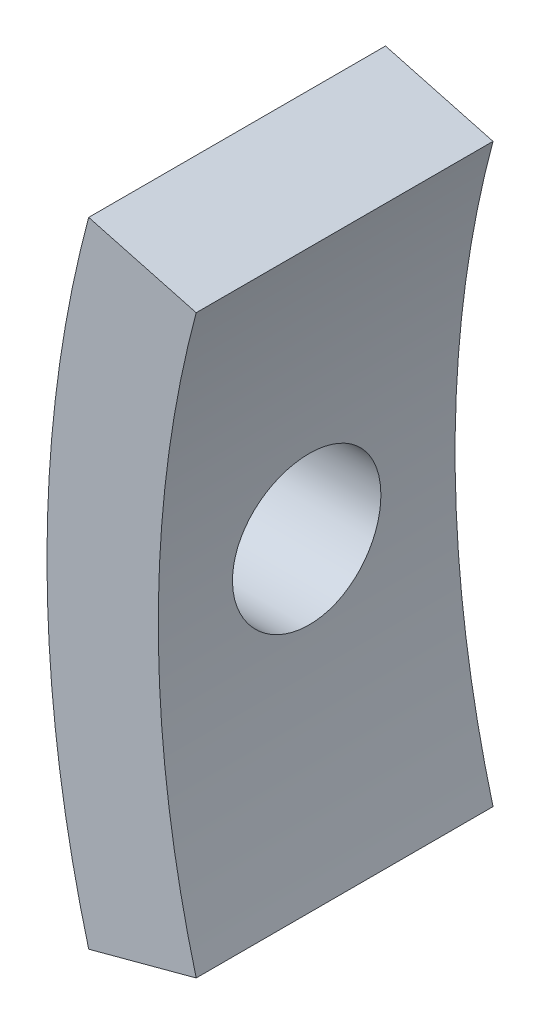
SolidWorks part; units mm, degrees
ref_plane "Front Plane" through (0, 0, 0) normal (1, 0, 0) x (0, 1, 0)
ref_plane "Top Plane" through (0, 0, 0) normal (0, 0, 1) x (0, 1, 0)
ref_plane "Right Plane" through (0, 0, 0) normal (0, 1, 0) x (-1, 0, 0)
sketch "Sketch1" plane through (0, 0, 0) normal (0, 0, 1) x (0, 1, 0)
  line L0 (0, 0) -> (-10.6763, 39.8444)
  line L1 (-10.6763, 39.8444) -> (10.6763, 39.8444)
  line L2 (10.6763, 39.8444) -> (0, 0)
  circle A0 centre (0, 0) radius 37.5
  circle A1 centre (0, 0) radius 41.25
  point P3 (13.7307, 38.8977)
  dimension "D1" = 75
  dimension "D2" = 82.5
  dimension "D3" = 30
extrude "Boss-Extrude1" add sketch "Sketch1" along normal blind 10 contours L1 A1 | A0 L2 L1 L0 region at (-38.4471, 0, 0) region at (-40.4075, 0, 0)
sketch "Sketch2" plane through (0, 0, 0) normal (1, 0, 0) x (0, 1, 0)
  line L0 (0, 0) -> (0, 5) construction
  line L1 (-9.7057, 0) -> (9.7057, 0) construction
  line L2 (0, 5) -> (0, 10) construction
  line L3 (9.7057, 10) -> (-9.7057, 10) construction
  circle A0 centre (0, 5) radius 2.5
  dimension "D1" = 5
extrude "Cut-Extrude1" cut sketch "Sketch2" along normal through all both and the other way through all
